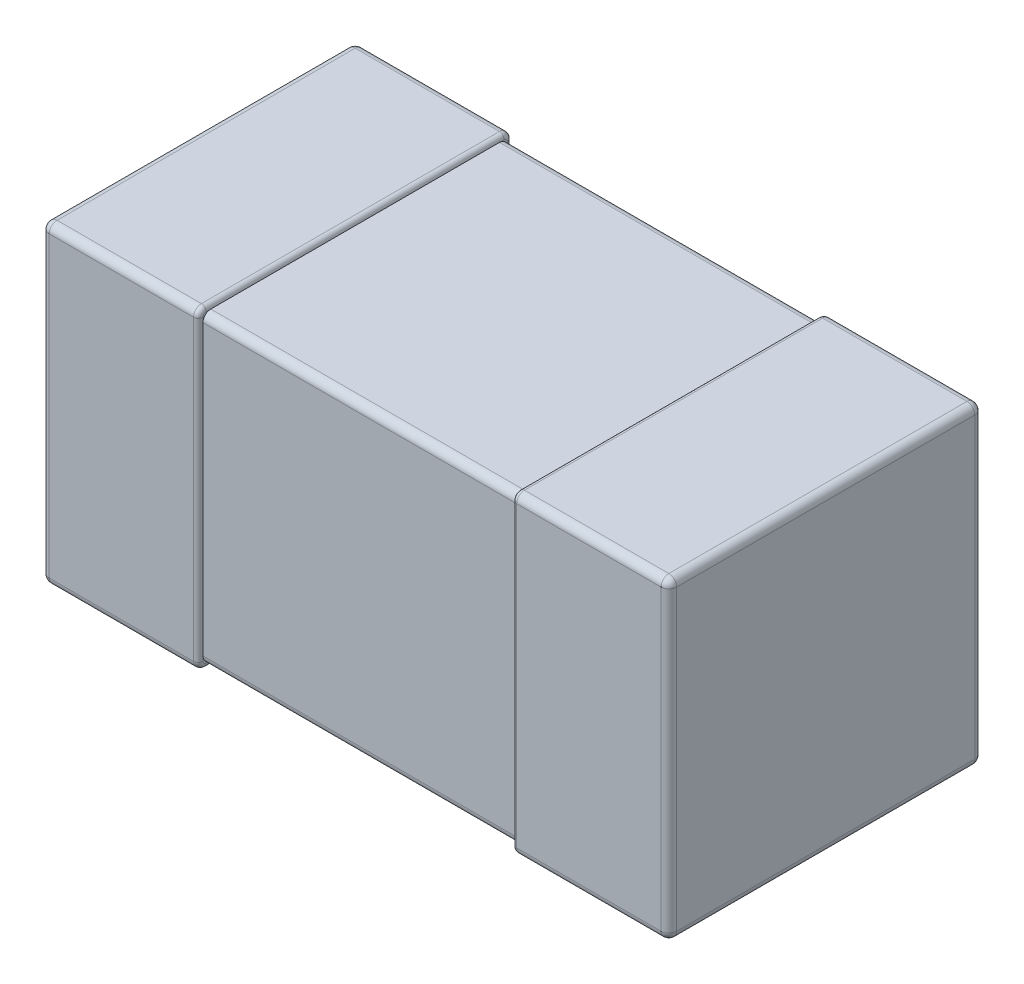
SolidWorks part; units mm, degrees
ref_plane "Top Plane" through (0, 0, 0) normal (0, 0, 1) x (1, 0, 0)
ref_plane "Front Plane" through (0, 0, 0) normal (0, 1, 0) x (1, 0, 0)
ref_plane "Side Plane" through (0, 0, 0) normal (1, 0, 0) x (0, 0, -1)
sketch "Sketch1" plane through (0, 0, 0) normal (0, 0, 1) x (1, 0, 0)
  line L1 (-0.2, 0.1) -> (0.2, 0.1)
  line L2 (-0.2, 0.1) -> (-0.2, -0.1)
  line L3 (-0.2, -0.1) -> (0.2, -0.1)
  line L4 (0.2, 0.1) -> (0.2, -0.1)
  dimension "D1" = 0.4
  dimension "D2" = 0.2
  dimension "D3" = 0.2
  dimension "D4" = 0.1
extrude "All body" add sketch "Sketch1" along normal blind 0.2
sketch "Sketch2" plane through (0, 0, 0) normal (1, 0, 0) x (0, 0, -1)
  line L14 (-0.003, 0.097) -> (-0.197, 0.097)
  line L15 (-0.003, -0.097) -> (-0.003, 0.097)
  line L16 (-0.197, -0.097) -> (-0.003, -0.097)
  line L17 (-0.197, 0.097) -> (-0.197, -0.097)
  line L18 (-0.003, 0.097) -> (-0.197, 0.097)
  line L19 (-0.003, -0.097) -> (-0.003, 0.097)
  line L20 (-0.197, -0.097) -> (-0.003, -0.097)
  line L21 (-0.197, 0.097) -> (-0.197, -0.097)
  dimension "D1" = 0.003
extrude "Cut out the body for pin" cut sketch "Sketch2" against normal blind 0.1 and the other way blind 0.1 flip side to cut
fillet "Body fillet" radius 0.005 4 edges at (0, 0.097, 0.003) (0, 0.097, 0.197) (0, -0.097, 0.003) (0, -0.097, 0.197)
fillet "Pin fillet a" radius 0.005 16 edges at (0.2, -0.1, 0.1) (0.2, 0, 0.2) (0.2, 0.1, 0.1) (0.2, 0, 0) (-0.2, 0.1, 0.1) (-0.2, 0, 0.2) (-0.2, -0.1, 0.1) (-0.2, 0, 0) (0.15, 0.1, 0.2) (0.15, -0.1, 0.2) (0.15, -0.1, 0) (0.15, 0.1, 0) (-0.15, 0.1, 0) (-0.15, -0.1, 0) (-0.15, 0.1, 0.2) (-0.15, -0.1, 0.2)
fillet "Pin fillet b" radius 0.003 16 edges at (0.1, -0.0985, 0.1985) (0.1, -0.1, 0.1) (0.1, -0.0985, 0.0015) (0.1, 0, 0) (0.1, 0.0985, 0.0015) (0.1, 0.1, 0.1) (0.1, 0.0985, 0.1985) (-0.1, -0.0985, 0.1985) (-0.1, -0.1, 0.1) (-0.1, -0.0985, 0.0015) (-0.1, 0, 0) (-0.1, 0.0985, 0.0015) (-0.1, 0.1, 0.1) (-0.1, 0.0985, 0.1985) (0.1, 0, 0.2) (-0.1, 0, 0.2)
